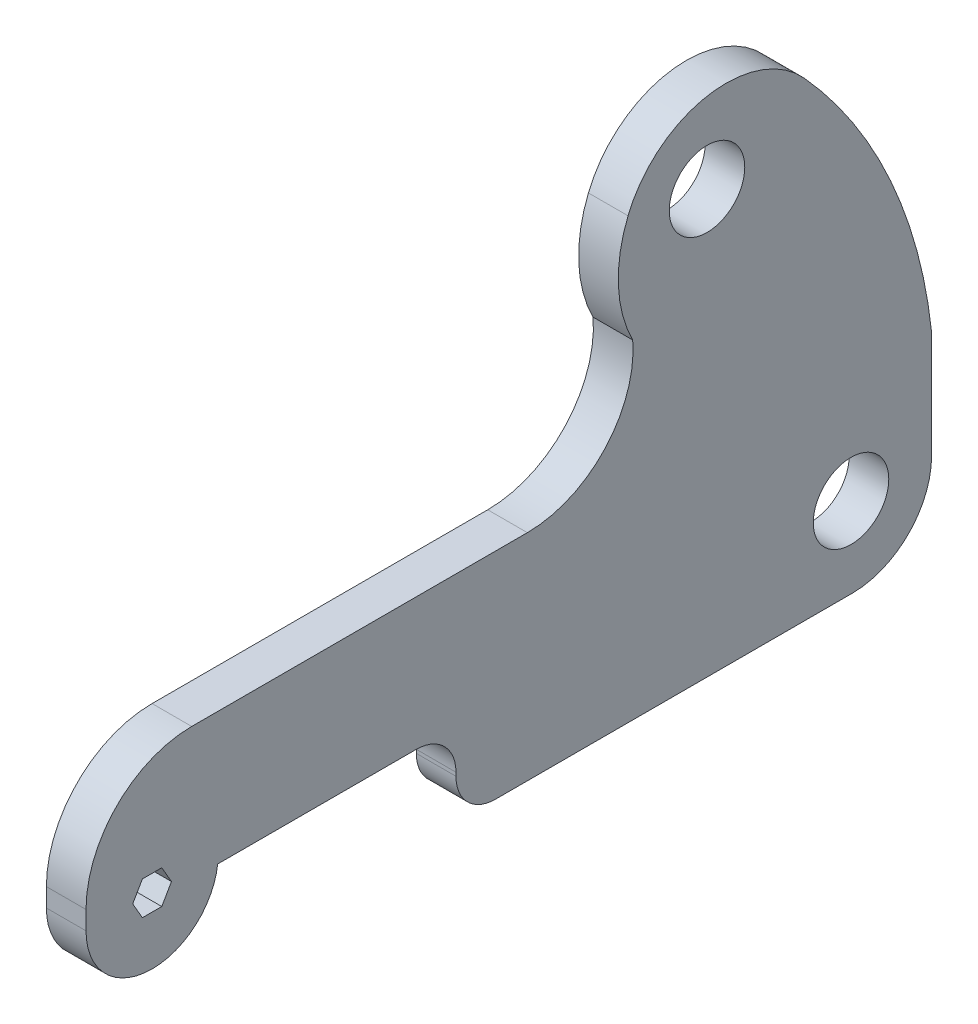
SolidWorks part; units mm, degrees
material "Cedro"
ref_plane "Alzado" through (0, 0, 0) normal (0, 0, 1) x (1, 0, 0)
ref_plane "Planta" through (0, 0, 0) normal (0, 1, 0) x (1, 0, 0)
ref_plane "Vista lateral" through (0, 0, 0) normal (1, 0, 0) x (0, 0, -1)
sketch "Croquis1" plane through (0, 0, 0) normal (1, 0, 0) x (0, 0, -1)
  line L0 (65, 25.4) -> (65, 281.0616)
  line L1 (65, 281.0616) -> (385, 281.0616)
  line L2 (385, 281.0616) -> (385, -8.9384)
  line L5 (115, 22.4) -> (205, 22.4)
  line L6 (205, 22.4) -> (205, -8.9384)
  line L7 (205, -8.9384) -> (385, -8.9384)
  line L8 (65, 25.4) -> (115, 25.4) construction
  line L9 (115, 25.4) -> (90, 25.4) construction
  line L10 (90, 25.4) -> (90, 0) construction
  line L11 (115, 22.4) -> (114.8193, 22.4)
  line L12 (82.6677, 25.4) -> (86.3338, 19.05)
  line L13 (86.3338, 19.05) -> (93.6662, 19.05)
  line L14 (93.6662, 19.05) -> (97.3323, 25.4)
  line L15 (97.3323, 25.4) -> (93.6662, 31.75)
  line L16 (93.6662, 31.75) -> (86.3338, 31.75)
  line L17 (86.3338, 31.75) -> (82.6677, 25.4)
  arc A0 (65, 25.4) -> (114.8193, 22.4) centre (90, 25.4) ccw
  circle A1 centre (90, 25.4) radius 6.35 construction
  dimension "D4" = 25
  dimension "D1" = 12.7
  dimension "D2" = 180
  dimension "D3" = 290
  dimension "D5" = 90
  dimension "D6" = 3
  dimension "D7" = 25.4
  dimension "D8" = 255.6616
extrude "Saliente-Extruir1" add sketch "Croquis1" along normal blind 15 contours L0 L1 L2 L7 L6 L5 L11 A0
sketch "Croquis2" plane through (0, 0, 0) normal (-1, 0, 0) x (0, 0, 1)
  line L1 (-82.6677, 25.4) -> (-86.3338, 31.75)
  line L2 (-86.3338, 31.75) -> (-93.6662, 31.75)
  line L3 (-93.6662, 31.75) -> (-97.3323, 25.4)
  line L4 (-97.3323, 25.4) -> (-93.6662, 19.05)
  line L5 (-93.6662, 19.05) -> (-86.3338, 19.05)
  line L6 (-86.3338, 19.05) -> (-82.6677, 25.4)
  circle A0 centre (-90, 25.4) radius 6.35 construction
  dimension "D1" = 12.7
extrude "Cortar-Extruir1" cut sketch "Croquis2" against normal through all
fillet "Redondeo1" radius 220 1 edges at (7.5, 281.0616, -385)
fillet "Redondeo2" radius 70 1 edges at (7.5, 281.0616, -65)
fillet "Redondeo3" radius 15 2 edges at (7.5, 22.4, -205) (7.5, -8.9384, -205)
fillet "Redondeo4" radius 30 1 edges at (7.5, -8.9384, -385)
sketch "Croquis7" plane through (15, 0, 0) normal (1, 0, 0) x (0, 0, -1)
  circle A0 centre (354.5, 21.5616) radius 14.29
extrude "Cortar-Extruir5" cut sketch "Croquis7" against normal through all
sketch "Croquis8" plane through (15, 0, 0) normal (1, 0, 0) x (0, 0, -1)
  circle A0 centre (300, 151.0616) radius 14.29
extrude "Cortar-Extruir6" cut sketch "Croquis8" against normal blind 523
sketch "Croquis9" plane through (15, 0, 0) normal (1, 0, 0) x (0, 0, -1)
  circle A0 centre (184.5, 231.0616) radius 14.29
extrude "Cortar-Extruir7" cut sketch "Croquis9" against normal blind 10
sketch "Croquis12" plane through (0, 0, 0) normal (-1, 0, 0) x (0, 0, 1)
  circle A0 centre (-267.4247, 207.1354) radius 12.5
  dimension "D1" = 25
extrude "Cortar-Extruir10" cut sketch "Croquis12" against normal blind 10
sketch "Croquis13" plane through (0, 0, 0) normal (-1, 0, 0) x (0, 0, 1)
  circle A0 centre (-263.1753, 232.1774) radius 2.02
  circle A1 centre (-271.6742, 182.0934) radius 2.02
  dimension "D1" = 4.04
extrude "Cortar-Extruir11" cut sketch "Croquis13" against normal blind 10
sketch "Croquis14" plane through (15, 0, 0) normal (1, 0, 0) x (0, 0, -1)
  line L0 (65, 72.4) -> (270, 72.4)
  line L1 (65, 25.4) -> (65, 211.0616) construction
  line L2 (190, 22.4) -> (114.8193, 22.4) construction
  line L3 (65, 72.4) -> (0, 212.5831)
  line L4 (0, 212.5831) -> (105.3354, 302.0886)
  line L5 (105.3354, 302.0886) -> (409.0379, 257.3358)
  line L6 (409.0379, 257.3358) -> (360.9592, 161.0616)
  arc A0 (270, 72.4) -> (271.8868, 115.6071) centre (204.4306, 96.9081) ccw
  arc A1 (271.8868, 115.6071) -> (360.9592, 161.0616) centre (316.423, 138.3344) cw
  arc A2 (385, 61.0616) -> (165, 281.0616) centre (165, 61.0616) ccw construction
  dimension "D4" = 50
  dimension "D5" = 70
  dimension "D1" = 50
  dimension "D2" = 205
  dimension "D3" = 120
  dimension "D6" = 100
extrude "Cortar-Extruir12" cut sketch "Croquis14" against normal through all
fillet "Redondeo5" radius 40 2 edges at (7.5, 72.4, -270) (7.5, 72.4, -65)
sketch "Croquis15" plane through (15, 0, 0) normal (1, 0, 0) x (0, 0, -1)
  line L0 (316.423, 188.3344) -> (358.6262, 190.9225)
  line L1 (358.6262, 190.9225) -> (422.7612, 101.2041)
  line L2 (422.7612, 101.2041) -> (385, 21.0616)
  arc A0 (385, 21.0616) -> (316.423, 188.3344) centre (196.0814, 41.3041) ccw
  arc A1 (360.9592, 161.0616) -> (271.8868, 115.6071) centre (316.423, 138.3344) ccw construction
  dimension "D1" = 190
extrude "Cortar-Extruir13" cut sketch "Croquis15" against normal through all
fillet "Redondeo6" radius 40 1 edges at (7.5, 188.3344, -316.423)
